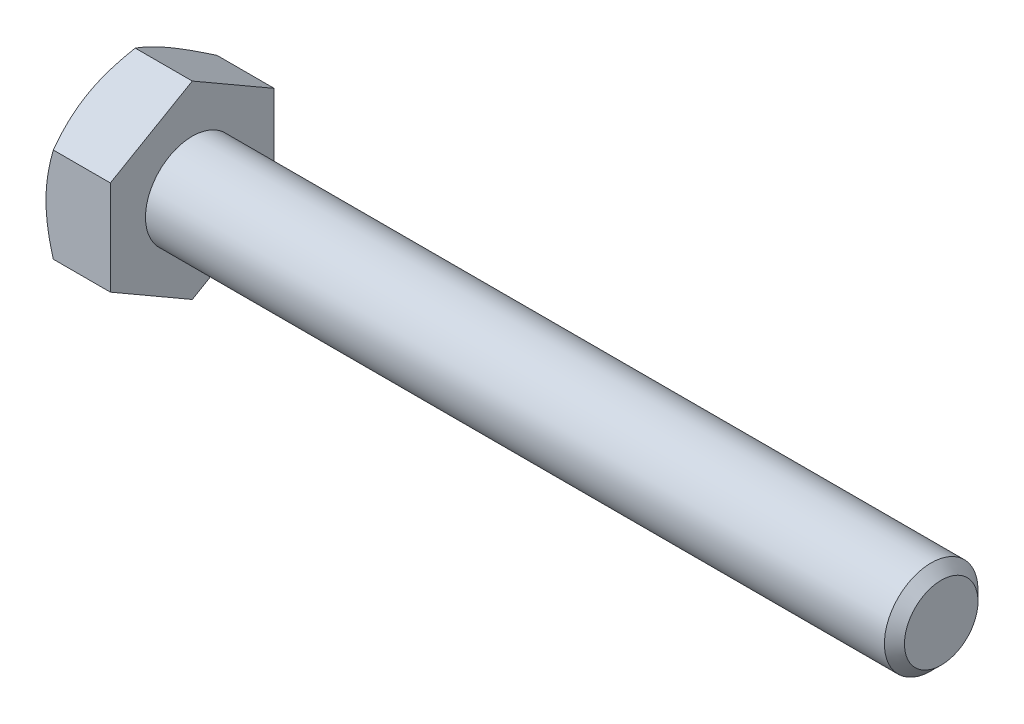
SolidWorks part; units mm, degrees
material "Alloy Steel"
ref_plane "Front Plane" through (0, 0, 0) normal (0, 0, 1) x (1, 0, 0)
ref_plane "Top Plane" through (0, 0, 0) normal (0, 1, 0) x (1, 0, 0)
ref_plane "Right Plane" through (0, 0, 0) normal (1, 0, 0) x (0, 0, -1)
sketch "Sketch1" plane through (0, 0, 0) normal (0, 0, 1) x (1, 0, 0)
  line L0 (-27.5828, 0) -> (27.5828, 0) construction
  line L1 (27.5828, 3.175) -> (27.5828, -3.175) construction
  line L2 (-23.2172, 5.5562) -> (-23.2172, -5.5562) construction
  line L3 (-27.5828, 5.5562) -> (-27.5828, -5.5562) construction
  point P9 (-23.2172, 0)
  point P10 (24.4078, -3.175)
  dimension "Screw Dia" = 6.35
  dimension "Hex" = 11.1125
  dimension "Head Ht" = 4.3656
  dimension "Screw Lenght" = 50.8
  dimension "D1" = 3.175
ref_plane "Plane2" through (27.5828, 0, 0) normal (1, 0, 0) x (0, 0, -1)
sketch "Sketch5" plane through (27.5828, 0, 0) normal (1, 0, 0) x (0, 0, -1)
  circle A0 centre (0, 0) radius 3.175
extrude "Boss-Extrude3" add sketch "Sketch5" against normal up to vertex (50.8 mm away) up to point (-23.2172, 0, 0)
sketch "Sketch9" plane through (27.5828, 0, 0) normal (1, 0, 0) x (0, 0, -1)
  circle A1 centre (0, 0) radius 3.175
  circle A2 centre (0, 0) radius 3.175
  dimension "D1" = 0
curve "Helix/Spiral1" [suppressed] pitch 0.9071 height 19.9571 turns 22 parameters "Pitch"=0.9071
chamfer "Chamfer1" distance 0.6804 angle 45 1 edges at (27.5828, 0, -3.175)
sketch "Sketch10" plane through (0, 0, 0) normal (0, 0, 1) x (1, 0, 0)
  line L0 (27.5828, 3.175) -> (27.923, 2.5858)
  line L1 (27.923, 2.5858) -> (28.0364, 2.5858)
  line L2 (28.0364, 2.5858) -> (28.3766, 3.175)
  line L3 (27.5828, 3.175) -> (28.3766, 3.175)
  line L4 (27.9797, 3.175) -> (27.9797, 2.5858) construction
  line L5 (27.7529, 2.8804) -> (28.2065, 2.8804) construction
  dimension "D1" = 60
  dimension "D2" = 0.1134
  dimension "D3" = 0.4536
sweep "Cut-Sweep1" [suppressed] cut profiles "Sketch10" path "Helix/Spiral1"
sketch "Sketch11" plane through (0, 0, 0) normal (0, 0, 1) x (1, 0, 0)
  line L0 (-23.2172, 3.175) -> (-23.2172, 0)
  line L1 (-23.2172, 0) -> (11.7078, 0)
  line L3 (11.7078, 0) -> (8.5328, 3.175)
  line L4 (-23.2172, 3.175) -> (8.5328, 3.175)
  dimension "D1" = 45
  dimension "MIn Thread" = 19.05
revolve "Revolve1" [suppressed] add sketch "Sketch11" angle 360 about L1
sketch "Sketch6" plane through (-23.2172, 0, 0) normal (-1, 0, 0) x (0, 0, 1)
  line L0 (0, 5.5562) -> (0, -5.5562) construction
  line L1 (5.5562, 3.2079) -> (0, 6.4158)
  line L2 (0, 6.4158) -> (-5.5562, 3.2079)
  line L3 (-5.5562, 3.2079) -> (-5.5562, -3.2079)
  line L4 (-5.5562, -3.2079) -> (0, -6.4158)
  line L5 (0, -6.4158) -> (5.5563, -3.2079)
  line L6 (5.5563, -3.2079) -> (5.5562, 3.2079)
  circle A0 centre (0, 0) radius 5.5562 construction
extrude "Boss-Extrude4" add sketch "Sketch6" along normal up to vertex (4.3656 mm away) up to point (-27.5828, -5.5562, 0)
sketch "Sketch7" plane through (-27.5828, 0, 0) normal (-1, 0, 0) x (0, 0, 1)
  circle A0 centre (0, 0) radius 5.5562 construction
  circle A1 centre (0, 0) radius 5.5562
sketch "Sketch8" plane through (-27.5828, 0, 0) normal (-1, 0, 0) x (0, 0, 1)
  circle A0 centre (0, 0) radius 5.5562 construction
  circle A1 centre (0, 0) radius 5.5562
extrude "Cut-Extrude3" cut sketch "Sketch8" against normal through all draft 60 flip side to cut
sketch "Sketch12" plane through (-27.5828, 0, 0) normal (-1, 0, 0) x (0, 0, 1)
  line L0 (0, 4.2783) -> (0, 2.3892) construction
  line L1 (0.1667, 4.2783) -> (0.1667, 2.3892)
  line L2 (-0.1667, 4.2783) -> (-0.1667, 2.3892)
  line L3 (0, 3.175) -> (0, -3.175) construction
  arc A0 (0.1667, 4.2783) -> (-0.1667, 4.2783) centre (0, 4.2783) ccw
  arc A1 (-0.1667, 2.3892) -> (0.1667, 2.3892) centre (0, 2.3892) ccw
  circle A3 centre (0, 0) radius 2.2225 construction
  circle A4 centre (0, 0) radius 4.445 construction
  point P2 (0, 3.3337)
  dimension "D1" = 4.445
  dimension "D3" = 8.89
  dimension "D2" = 0.3334
extrude "Cut-Extrude4" [suppressed] cut sketch "Sketch12" against normal blind 0.254
pattern_circular "CirPattern1" [suppressed] count 6 over 360 of bodies 116
equation "\"D2@Sketch10\" = \"Pitch@Helix/Spiral1\"*.125"
equation "\"D3@Sketch10\" = \"Pitch@Helix/Spiral1\"*.5"
equation "\"D3@Helix/Spiral1\" = \"MIn Thread@Sketch11\"+\"Pitch@Helix/Spiral1\""
equation "\"D1@Chamfer1\" = \"Pitch@Helix/Spiral1\"*.75"
equation "\"D1@Sketch12\" = \"Hex@Sketch1\"*.4"
equation "\"D3@Sketch12\" = \"Hex@Sketch1\"*.8"
equation "\"D2@Sketch12\" = \"Hex@Sketch1\"*.03"
equation "\"D1@Sketch1\" = \"Pitch@Helix/Spiral1\"*3.5"
